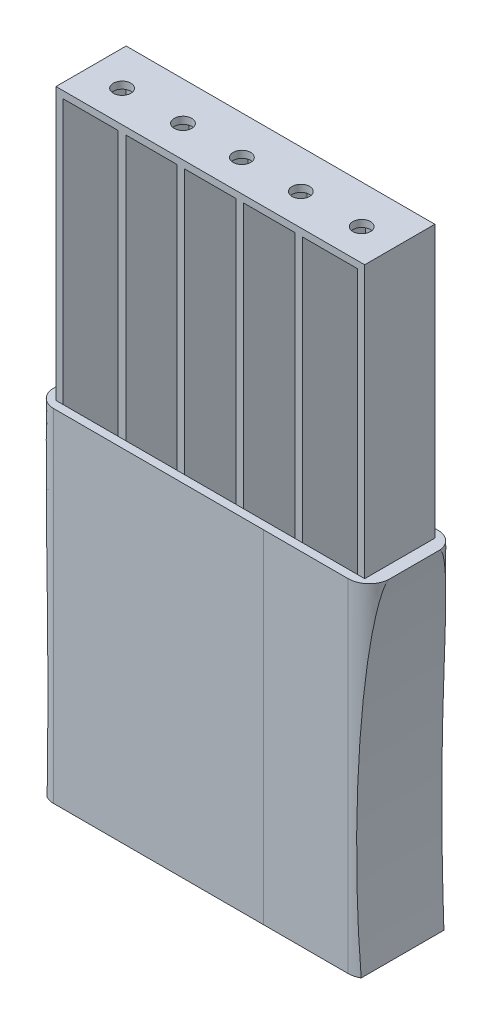
SolidWorks part; units mm, degrees
ref_plane "Front Plane" through (0, 0, 0) normal (0, 0, 1) x (1, 0, 0)
ref_plane "Top Plane" through (0, 0, 0) normal (0, 1, 0) x (1, 0, 0)
ref_plane "Right Plane" through (0, 0, 0) normal (1, 0, 0) x (0, 0, -1)
ref_plane "Plane1" through (0, 10, 0) normal (0, 1, 0) x (1, 0, 0)
sketch "Sketch1" plane through (0, 0, 0) normal (0, 0, 1) x (1, 0, 0)
  line L1 (-44, -87.5) -> (44, -87.5)
  line L2 (-44, -87.5) -> (-44, 87.5)
  line L3 (-44, 87.5) -> (44, 87.5)
  line L4 (44, -87.5) -> (44, 87.5)
  line L5 (-44, -87.5) -> (44, 87.5) construction
  line L6 (-44, 87.5) -> (44, -87.5) construction
  point P0 (0, 0)
  dimension "D1" = 88
  dimension "D2" = 175
extrude "Boss-Extrude1" add sketch "Sketch1" along normal blind 2
sketch "Sketch2" plane through (0, 0, 2) normal (0, 0, 1) x (1, 0, 0)
  line L4 (44, -87.5) -> (44, 87.5)
  line L5 (44, 87.5) -> (-44, 87.5)
  line L6 (-44, 87.5) -> (-44, -87.5)
  line L7 (-44, -87.5) -> (44, -87.5)
  line L8 (44, -87.5) -> (44, 87.5)
  line L9 (44, 87.5) -> (-44, 87.5)
  line L10 (-44, 87.5) -> (-44, -87.5)
  line L11 (-44, -87.5) -> (44, -87.5)
  dimension "D1" = 0
extrude "Extrude-Thin1" add sketch "Sketch2" along normal blind 18 thin thin type one direction reverse wall 2
sketch "Sketch7" plane through (0, 10, 0) normal (0, -1, 0) x (1, 0, 0)
  line L10 (-42.3768, -2.407) -> (42.5401, -2.407)
  line L11 (47.6224, 2.5172) -> (47.6224, 16.4468)
  line L12 (41.5429, 22.3538) -> (17.5198, 22.3437)
  line L13 (17.5198, 22.3437) -> (-42.3262, 22.3337)
  line L14 (-47.3776, 17.3465) -> (-47.3776, 2.5515)
  spline S8 degree 3 poles (42.5401, -2.407) (42.8706, -2.4078) (43.196, -2.3778) (43.8369, -2.2583) (44.1553, -2.1674) (44.7669, -1.9274) (45.0576, -1.7798) (45.6085, -1.4299) (45.8711, -1.2247) (46.3442, -0.773) (46.5566, -0.526) (46.8382, -0.1231) (46.9263, 0.0175) (47.0866, 0.3047) (47.159, 0.4514) (47.3532, 0.9003) (47.4524, 1.2115) (47.5875, 1.8587) (47.6216, 2.1864) (47.6224, 2.5172) knots 0 0 0 0 0.125 0.125 0.25 0.25 0.375 0.375 0.5 0.5 0.625 0.625 0.6875 0.6875 0.75 0.75 0.875 0.875 1 1 1 1
  spline S9 degree 3 poles (47.6224, 16.4468) (47.6224, 16.843) (47.5828, 17.2324) (47.4656, 17.8067) (47.4168, 17.9965) (47.2994, 18.3728) (47.2305, 18.5591) (46.9987, 19.1005) (46.8095, 19.4421) (46.474, 19.926) (46.3528, 20.0833) (46.0967, 20.383) (45.962, 20.5254) (45.5387, 20.9312) (45.2308, 21.1731) (44.563, 21.5988) (44.2136, 21.7758) (43.4861, 22.0621) (43.1044, 22.1719) (42.3303, 22.3175) (41.9388, 22.3539) (41.5429, 22.3538) knots 0 0 0 0 0.125 0.125 0.1875 0.1875 0.25 0.25 0.375 0.375 0.4375 0.4375 0.5 0.5 0.625 0.625 0.75 0.75 0.875 0.875 1 1 1 1
  spline S10 degree 3 poles (-42.3262, 22.3337) (-42.6576, 22.3345) (-42.9836, 22.3031) (-43.4649, 22.2099) (-43.624, 22.171) (-43.9396, 22.0774) (-44.0966, 22.0224) (-44.5538, 21.8366) (-44.8431, 21.6848) (-45.3911, 21.3255) (-45.6513, 21.1158) (-46.1184, 20.6569) (-46.3281, 20.4063) (-46.6064, 19.998) (-46.6931, 19.856) (-46.8504, 19.5673) (-46.9214, 19.4199) (-47.1124, 18.9685) (-47.2104, 18.6543) (-47.3432, 18.0058) (-47.3769, 17.678) (-47.3776, 17.3465) knots 0 0 0 0 0.125 0.125 0.1875 0.1875 0.25 0.25 0.375 0.375 0.5 0.5 0.625 0.625 0.6875 0.6875 0.75 0.75 0.875 0.875 1 1 1 1
  spline S11 degree 3 poles (-47.3776, 2.5515) (-47.3776, 2.223) (-47.3453, 1.9) (-47.25, 1.4233) (-47.2104, 1.2658) (-47.1151, 0.9534) (-47.0592, 0.7983) (-46.8708, 0.3471) (-46.717, 0.0618) (-46.3535, -0.4777) (-46.142, -0.7328) (-45.6803, -1.1896) (-45.4283, -1.3943) (-44.8814, -1.7557) (-44.5911, -1.9086) (-43.9903, -2.1544) (-43.6758, -2.2489) (-43.0316, -2.3754) (-42.706, -2.407) (-42.3768, -2.407) knots 0 0 0 0 0.125 0.125 0.1875 0.1875 0.25 0.25 0.375 0.375 0.5 0.5 0.625 0.625 0.75 0.75 0.875 0.875 1 1 1 1
extrude "Boss-Extrude2" add sketch "Sketch7" along normal up to surface (97.5 mm away) up to face at (0, -87.5, 10)
sketch "Sketch10" plane through (0, 0, 2) normal (0, 0, -1) x (-1, 0, 0)
  line L8 (42, -85.5) -> (42, 85.5)
  line L9 (-42, -85.5) -> (42, -85.5)
  line L10 (-42, 85.5) -> (-42, -85.5)
  line L11 (42, 85.5) -> (-42, 85.5)
extrude "Cut-Extrude2" cut sketch "Sketch10" against normal up to surface (18 mm away) up to face at (0, 48.25, 20)
sketch "Sketch3" plane through (0, 0, 2) normal (0, 0, 1) x (1, 0, 0)
  line L0 (-25.2, 85.5) -> (-25.2, -85.5)
  line L1 (42, 85.5) -> (-42, 85.5) construction
  line L3 (-8.4, 85.5) -> (-8.4, -85.5)
  line L4 (42, 85.5) -> (-42, 85.5) construction
  line L5 (25.2, 85.5) -> (25.2, -85.5)
  line L6 (8.4, 85.5) -> (8.4, -85.5)
  line L8 (-42, 85.5) -> (-42, -85.5) construction
  line L9 (42, -85.5) -> (42, 85.5) construction
  line L11 (42, -85.5) -> (-42, -85.5) construction
  point P4 (25.2, -85.5)
  point P14 (8.4, -85.5)
  point P15 (0, 0)
  point P20 (0, 0)
  point P21 (-25.2, -85.5)
  point P23 (0, 0)
  point P25 (0, 0)
  point P26 (-8.4, -85.5)
  point P27 (0, 0)
  dimension "D1" = 16.8
  dimension "D2" = 16.8
  dimension "D3" = 16.8
  dimension "D4" = 16.8
  dimension "D5" = 16.8
extrude "Extrude-Thin2" add sketch "Sketch3" along normal blind 18 thin thin type mid plane wall 2.2
sketch "Sketch4" plane through (0, 87.5, 0) normal (0, 1, 0) x (1, 0, 0)
  line L0 (26.3, -20) -> (26.3, -2) construction
  line L1 (26.3, -2) -> (42, -2) construction
  line L2 (42, -2) -> (42, -20) construction
  line L3 (42, -20) -> (26.3, -20) construction
  line L4 (9.5, -20) -> (9.5, -2) construction
  line L5 (9.5, -2) -> (24.1, -2) construction
  line L6 (24.1, -2) -> (24.1, -20) construction
  line L7 (24.1, -20) -> (9.5, -20) construction
  line L8 (-7.3, -2) -> (7.3, -2) construction
  line L9 (7.3, -2) -> (7.3, -20) construction
  line L10 (7.3, -20) -> (-7.3, -20) construction
  line L11 (-7.3, -20) -> (-7.3, -2) construction
  line L12 (-24.1, -2) -> (-9.5, -2) construction
  line L13 (-9.5, -2) -> (-9.5, -20) construction
  line L14 (-9.5, -20) -> (-24.1, -20) construction
  line L15 (-24.1, -20) -> (-24.1, -2) construction
  line L16 (-42, -2) -> (-26.3, -2) construction
  line L17 (-26.3, -2) -> (-26.3, -20) construction
  line L18 (-26.3, -20) -> (-42, -20) construction
  line L19 (-42, -20) -> (-42, -2) construction
  line L20 (26.3, -20) -> (26.3, -2) construction
  line L21 (26.3, -2) -> (42, -2) construction
  line L22 (42, -2) -> (42, -20) construction
  line L23 (42, -20) -> (26.3, -20) construction
  line L24 (9.5, -20) -> (9.5, -2) construction
  line L25 (9.5, -2) -> (24.1, -2) construction
  line L26 (24.1, -2) -> (24.1, -20) construction
  line L27 (24.1, -20) -> (9.5, -20) construction
  line L28 (-7.3, -2) -> (7.3, -2) construction
  line L29 (7.3, -2) -> (7.3, -20) construction
  line L30 (7.3, -20) -> (-7.3, -20) construction
  line L31 (-7.3, -20) -> (-7.3, -2) construction
  line L32 (-24.1, -2) -> (-9.5, -2) construction
  line L33 (-9.5, -2) -> (-9.5, -20) construction
  line L34 (-9.5, -20) -> (-24.1, -20) construction
  line L35 (-24.1, -20) -> (-24.1, -2) construction
  line L36 (-42, -2) -> (-26.3, -2) construction
  line L37 (-26.3, -2) -> (-26.3, -20) construction
  line L38 (-26.3, -20) -> (-42, -20) construction
  line L39 (-42, -20) -> (-42, -2) construction
  line L40 (42, -11) -> (-42, -11) construction
  line L41 (-16.8, -20) -> (-16.8, -2) construction
  line L42 (-34.15, -20) -> (-34.15, -2) construction
  line L43 (0, -20) -> (0, -2) construction
  line L44 (16.8, -20) -> (16.8, -2) construction
  line L45 (34.15, -20) -> (34.15, -2) construction
  point P26 (34.15, -11)
  point P28 (16.8, -11)
  point P30 (0, -11)
  point P31 (-16.8, -11)
  point P34 (-34.15, -11)
hole_wizard "Ø5.0mm Dowel Hole3" positions "Sketch5" profile "Sketch6" hole size "Ø5.0" standard "BSI" end condition up to next
sketch "Sketch5" plane through (0, 87.5, 0) normal (0, 1, 0) x (1, 0, 0)
  line L0 (-34.15, -20) -> (-34.15, -2) construction
  line L1 (-16.8, -20) -> (-16.8, -2) construction
  point P0 (-34.15, -11)
  point P4 (-16.8, -11)
  point P8 (0, -11)
  point P11 (16.8, -11)
  point P14 (34.15, -11)
sketch "Sketch6" plane through (-34.15, 87.5, 11) normal (1, 0, 0) x (0, 0, 1)
  line L0 (0, 0) -> (0, 2)
  line L1 (0, 2) -> (2.5, 2)
  line L2 (2.5, 2) -> (2.5, 0)
  line L5 (2.5, 0) -> (0, 0)
  line L11 (0, -6.35) -> (0, 107.95) construction
  dimension "Thru Hole Dia." = 5
  dimension "Thru Hole Depth" = 2
sketch "Sketch11" plane through (0, 0, 0) normal (0, 0, 1) x (1, 0, 0)
  line L0 (-47.3776, -87.5) -> (-47.3776, 10) construction
  line L1 (47.6224, -87.5) -> (47.6224, 10) construction
  line L2 (-47.3776, -87.5) -> (-47.3776, 10) construction
  line L3 (47.6224, -87.5) -> (47.6224, 10) construction
  line L6 (-42.3262, -87.5) -> (-42.3262, 10) construction
  line L7 (41.5429, -87.5) -> (41.5429, 10) construction
  line L8 (-47.3776, 10) -> (-88.5977, 10)
  line L9 (13.6518, 10) -> (-13.6518, 10) construction
  line L10 (-88.5977, 10) -> (-88.5977, -88.3549)
  line L11 (-88.5977, -88.3549) -> (-44.8519, -87.5)
  line L12 (47.6224, 10) -> (76.6267, 12.525)
  line L13 (76.6267, 12.525) -> (69.1799, -99.2923)
  line L14 (69.1799, -99.2923) -> (44.5826, -87.5)
  line L15 (-47.3776, -87.5) -> (-42.3262, -87.5) construction
  line L16 (41.5429, -87.5) -> (47.6224, -87.5) construction
  spline S0 degree 2 poles (-47.3776, 10) (-43.3223, -38.6841) (-44.8519, -87.5) knots 0 0 0 1 1 1
  spline S1 degree 2 poles (47.6224, 10) (41.8008, -38.6312) (44.5826, -87.5) knots 0 0 0 1 1 1
  point P15 (-44.8519, -87.5)
  point P23 (44.0659, -87.5)
  point P24 (44.5826, -87.5)
  dimension "D1" = 2.3
  dimension "D2" = 2.3
extrude "Cut-Extrude3" cut sketch "Sketch11" against normal through all both and the other way through all
